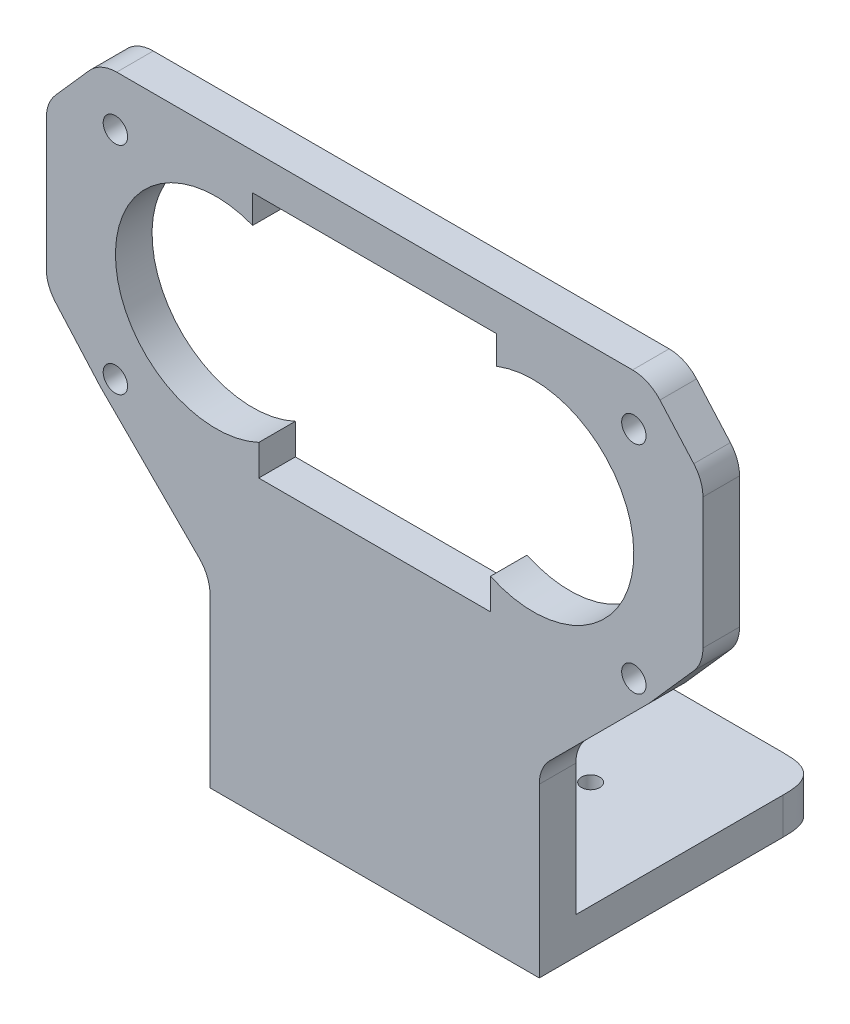
SolidWorks part; units mm, degrees
ref_plane "前视基准面" through (0, 0, 0) normal (0, 0, 1) x (1, 0, 0)
ref_plane "上视基准面" through (0, 0, 0) normal (0, 1, 0) x (1, 0, 0)
ref_plane "右视基准面" through (0, 0, 0) normal (1, 0, 0) x (0, 0, -1)
other "Configuration Table"
sketch "草图1" plane through (0, 0, 0) normal (0, 0, 1) x (1, 0, 0)
  line L0 (0, 0) -> (0, 10) construction
  line L1 (0, 10) -> (-13, 10) construction
  line L2 (0, 10) -> (13, 10) construction
  line L3 (0, 0) -> (-22.5, 0) construction
  line L4 (-22.5, 0) -> (-22.5, 20) construction
  line L5 (-10, 20) -> (10, 20)
  line L6 (22.5, 20) -> (22.5, 0) construction
  line L7 (22.5, 0) -> (0, 0) construction
  line L8 (-10, 17.6852) -> (-10, 20)
  line L9 (-10, 23) -> (-21.148, 23)
  line L10 (-23.3955, 21.9871) -> (-26.1681, 18.8511)
  line L11 (-22.5, 0) -> (-26.1681, 4.1489)
  line L12 (-26.9205, 6.136) -> (-26.9205, 16.864)
  line L13 (-22.5, 0) -> (-14.3787, -8.1213)
  line L14 (-13.5, -10.2426) -> (-13.5, -24)
  line L15 (-13.5, -24) -> (13.5, -24)
  line L16 (-9.5, 2.5292) -> (-9.5, 0)
  line L17 (-9.5, 0) -> (9.5, 0)
  line L18 (23.3955, 21.9871) -> (26.1681, 18.8511)
  line L19 (26.9205, 6.136) -> (26.9205, 16.864)
  line L20 (22.5, 0) -> (26.1681, 4.1489)
  line L21 (22.5, 0) -> (14.3787, -8.1213)
  line L22 (13.5, -10.2426) -> (13.5, -24)
  line L23 (9.5, 2.5292) -> (9.5, 0)
  line L24 (10, 17.6852) -> (10, 20)
  line L25 (10, 23) -> (21.148, 23)
  line L26 (-10, 23) -> (10, 23)
  arc A0 (-10, 17.6852) -> (-9.5, 2.5292) centre (-13, 10) ccw
  arc A1 (9.5, 2.5292) -> (10, 17.6852) centre (13, 10) ccw
  arc A2 (10, 17.6852) -> (9.5, 2.5292) centre (13, 10) cw
  arc A3 (-14.3787, -8.1213) -> (-13.5, -10.2426) centre (-16.5, -10.2426) cw
  arc A4 (14.3787, -8.1213) -> (13.5, -10.2426) centre (16.5, -10.2426) ccw
  arc A5 (26.9205, 6.136) -> (26.1681, 4.1489) centre (23.9205, 6.136) cw
  arc A6 (26.1681, 18.8511) -> (26.9205, 16.864) centre (23.9205, 16.864) cw
  arc A7 (23.3955, 21.9871) -> (21.148, 23) centre (21.148, 20) ccw
  arc A8 (-26.1681, 4.1489) -> (-26.9205, 6.136) centre (-23.9205, 6.136) cw
  arc A9 (-26.1681, 18.8511) -> (-26.9205, 16.864) centre (-23.9205, 16.864) ccw
  arc A10 (-21.148, 23) -> (-23.3955, 21.9871) centre (-21.148, 20) ccw
  point P25 (0, -24)
  point P32 (-13.5, -9)
  point P35 (13.5, -9)
  point P38 (26.9205, 5)
  point P41 (26.9205, 18)
  point P44 (22.5, 23)
  point P47 (-26.9205, 5)
  point P50 (-26.9205, 18)
  point P53 (-22.5, 23)
  dimension "D2" = 16.5
  dimension "D4" = 20
  dimension "D12" = 3
  dimension "D1" = 13
  dimension "D3" = 10
  dimension "D5" = 45
  dimension "D6" = 10
  dimension "D7" = 15
  dimension "D8" = 24
  dimension "D9" = 5
  dimension "D10" = 5
  dimension "D11" = 13
extrude "凸台-拉伸1" add sketch "草图1" along normal blind 3 contours L26 L9 L10 L12 L11 L13 L14 L15 L22 L21 L20 L19 L18 L25 A1 L23 L17 L16 A0 L8 L5 L24 region at (0, -1.1621, 0)
sketch "草图2" plane through (0, 0, 0) normal (0, 0, -1) x (-1, 0, 0)
  line L0 (-13.5, -24) -> (-13.5, -21)
  line L1 (-13.5, -10.2426) -> (-13.5, -24) construction
  line L2 (-13.5, -21) -> (13.5, -21)
  line L3 (13.5, -10.2426) -> (13.5, -24) construction
  line L4 (13.5, -21) -> (13.5, -24)
  line L5 (13.5, -24) -> (-13.5, -24)
  dimension "D1" = 3
extrude "凸台-拉伸2" add sketch "草图2" along normal blind 20
fillet "圆角1" radius 3 1 edges at (13.5, -22.5, -20) curvature continuous yes
fillet "圆角2" radius 3 1 edges at (-13.5, -22.5, -20) curvature continuous yes
sketch "草图3" plane through (0, -21, 0) normal (0, 1, 0) x (1, 0, 0)
  line L2 (0, 0) -> (0, 17.6116) construction
  line L6 (-13.5, 17) -> (-13.5, 0) construction
  circle A0 centre (0, 10) radius 2.5
  circle A1 centre (-4.71, 10) radius 0.75
  circle A2 centre (0, 14.32) radius 0.75
  circle A4 centre (0, 5.68) radius 0.75
  circle A5 centre (4.71, 10) radius 0.75
  dimension "D1" = 5
  dimension "D7" = 1.5
  dimension "D2" = 4.71
  dimension "D3" = 10
  dimension "D4" = 13.5
  dimension "D5" = 4.32
  dimension "D6" = 4.32
extrude "切除-拉伸1" cut sketch "草图3" against normal blind 20
sketch "草图4" plane through (0, 0, 3) normal (0, 0, 1) x (1, 0, 0)
  line L0 (0, 23) -> (0, -24) construction
  line L1 (-21.255, 18.855) -> (21.255, 18.855) construction
  line L2 (-21.255, 18.855) -> (-21.255, 1.145) construction
  line L3 (-21.255, 1.145) -> (21.255, 1.145) construction
  line L4 (21.255, 18.855) -> (21.255, 1.145) construction
  line L7 (-13, 10) -> (13.9139, 10) construction
  line L11 (13.5, -10.2426) -> (13.5, -24) construction
  line L12 (-13.5, -10.2426) -> (-13.5, -24) construction
  circle A2 centre (-21.255, 18.855) radius 1
  circle A3 centre (-21.255, 1.145) radius 1
  circle A4 centre (21.255, 18.855) radius 1
  circle A5 centre (21.255, 1.145) radius 1
  dimension "D3" = 2
  dimension "D1" = 17.71
  dimension "D2" = 42.51
extrude "切除-拉伸2" cut sketch "草图4" against normal blind 10
